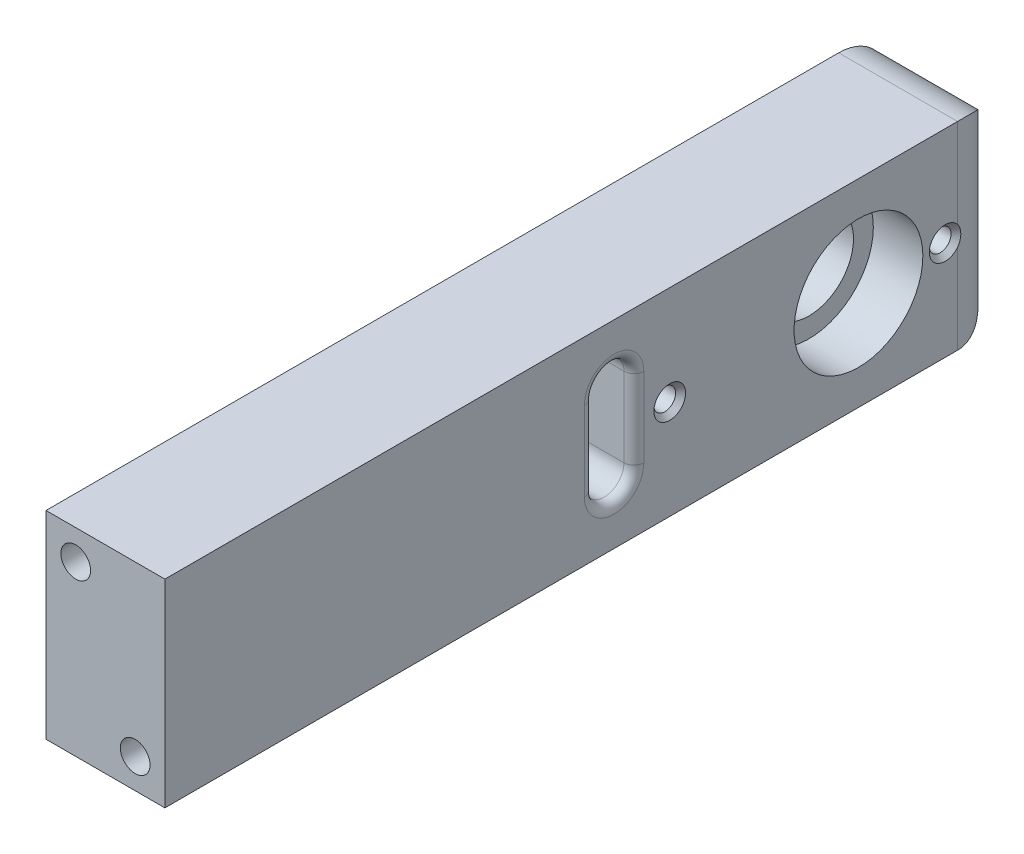
SolidWorks part; units mm, degrees
ref_plane "Płaszczyzna przednia" through (0, 0, 0) normal (0, 0, 1) x (1, 0, 0)
ref_plane "Płaszczyzna górna" through (0, 0, 0) normal (0, 1, 0) x (1, 0, 0)
ref_plane "Płaszczyzna prawa" through (0, 0, 0) normal (1, 0, 0) x (0, 0, -1)
sketch "Szkic1" plane through (0, 0, 0) normal (0, 0, 1) x (1, 0, 0)
  line L1 (-6, -10) -> (6, -10)
  line L2 (-6, -10) -> (-6, 10)
  line L3 (-6, 10) -> (6, 10)
  line L4 (6, -10) -> (6, 10)
  line L5 (-6, -10) -> (6, 10) construction
  line L6 (-6, 10) -> (6, -10) construction
  point P0 (0, 0)
  dimension "D1" = 20
  dimension "D2" = 12
extrude "Dodanie-wyciągnięcie1" add sketch "Szkic1" along normal blind 85
sketch "Szkic2" plane through (0, 0, 85) normal (0, 0, 1) x (1, 0, 0)
  line L0 (6, -10) -> (6, 10) construction
  line L1 (-6, -10) -> (6, -10) construction
  line L2 (-6, 10) -> (-6, -10) construction
  line L3 (6, 10) -> (-6, 10) construction
  circle A0 centre (-3, 7) radius 1.5
  circle A1 centre (3, -7) radius 1.5
  dimension "D1" = 3
  dimension "D2" = 3
  dimension "D3" = 3
  dimension "D4" = 3
  dimension "D5" = 3
  dimension "D6" = 3
extrude "Wytnij-wyciągnięcie1" cut sketch "Szkic2" against normal blind 10
sketch "Szkic4" plane through (6, 0, 0) normal (1, 0, 0) x (0, 0, -1)
  line L0 (-85, 10) -> (0, 10) construction
  line L1 (-85, -10) -> (-85, 10) construction
  circle A0 centre (-15, 0) radius 6.5
  dimension "D1" = 13
  dimension "D2" = 10
  dimension "D3" = 70
extrude "Wytnij-wyciągnięcie2" cut sketch "Szkic4" against normal blind 5
sketch "Szkic5" plane through (-6, 0, 0) normal (-1, 0, 0) x (0, 0, 1)
  line L0 (85, -10) -> (0, -10) construction
  line L1 (85, 10) -> (85, -10) construction
  circle A0 centre (15, 0) radius 4.5
  dimension "D1" = 9
  dimension "D2" = 10
  dimension "D3" = 70
extrude "Wytnij-wyciągnięcie3" cut sketch "Szkic5" against normal through all
sketch "Szkic6" plane through (-6, 0, 0) normal (-1, 0, 0) x (0, 0, 1)
  circle A0 centre (34.05, 0) radius 1.1
extrude "Wytnij-wyciągnięcie4" cut sketch "Szkic6" against normal through all
chamfer "Sfazowanie1" distance 0.5 angle 45 1 edges at (6, 0, 35.15)
sketch "Szkic7" plane through (-6, 0, 0) normal (-1, 0, 0) x (0, 0, 1)
  circle A0 centre (6.25, 0) radius 1.1
extrude "Wytnij-wyciągnięcie5" cut sketch "Szkic7" against normal through all
chamfer "Sfazowanie2" distance 0.5 angle 45 1 edges at (6, 0, 7.35)
fillet "Zaokrąglenie1" radius 5 3 edges at (6, 0, 0) (0, 10, 0) (0, -10, 0)
sketch "Szkic8" plane through (-6, 0, 0) normal (-1, 0, 0) x (0, 0, 1)
  line L0 (39.668, -4) -> (39.668, 4) construction
  line L1 (37.668, -4) -> (37.668, 4)
  line L2 (41.668, -4) -> (41.668, 4)
  line L3 (85, 10) -> (5, 10) construction
  arc A0 (37.668, -4) -> (41.668, -4) centre (39.668, -4) ccw
  arc A1 (41.668, 4) -> (37.668, 4) centre (39.668, 4) ccw
  point P2 (39.668, 0)
  dimension "D3" = 2
  dimension "D1" = 8
  dimension "D2" = 10
extrude "Wytnij-wyciągnięcie6" cut sketch "Szkic8" against normal through all
fillet "Zaokrąglenie2" radius 1 8 edges at (-6, 0, 41.668) (-6, -6, 39.668) (-6, 0, 37.668) (6, 6, 39.668) (6, 0, 41.668) (6, -6, 39.668) (-6, 6, 39.668) (6, 0, 37.668)
